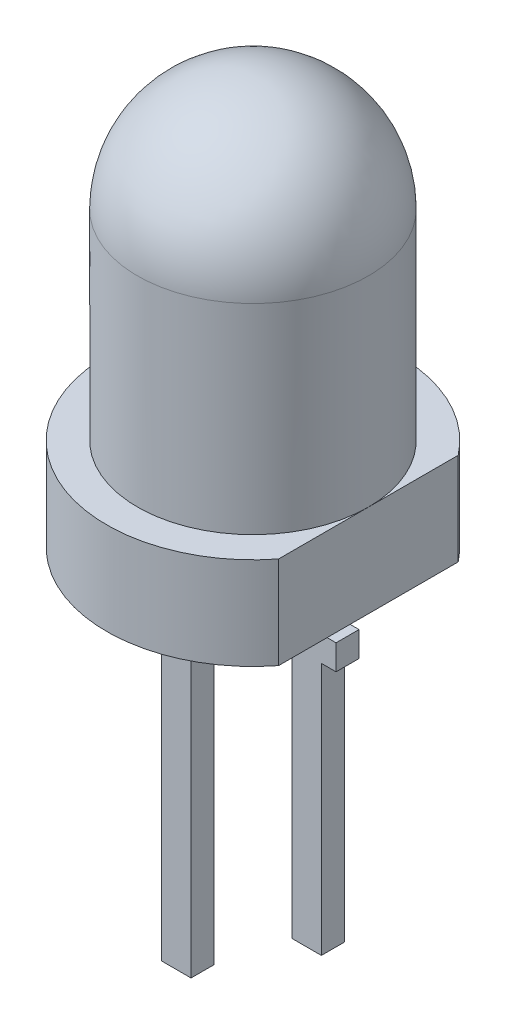
SolidWorks part; units mm, degrees
ref_plane "Front Plane" through (0, 0, 0) normal (0, 0, 1) x (1, 0, 0)
ref_plane "Top Plane" through (0, 0, 0) normal (0, 1, 0) x (1, 0, 0)
ref_plane "Right Plane" through (0, 0, 0) normal (1, 0, 0) x (0, 0, -1)
sketch "Sketch1" plane through (0, 0, 0) normal (0, 0, 1) x (1, 0, 0)
  line L0 (0, 0) -> (0, 27.4114) construction
  line L1 (0, 0) -> (-1.9, 0)
  line L2 (-1.9, 0) -> (-1.9, 1.2)
  line L3 (-1.9, 1.2) -> (-1.5, 1.2)
  line L4 (-1.5, 5.3) -> (-4.9108, 5.3) construction
  line L5 (-1.5, 1.2) -> (-1.5, 3.8)
  line L6 (0, 0) -> (0, 5.3)
  arc A0 (-1.5, 3.8) -> (0, 5.3) centre (0, 3.8) cw
  point P9 (-1.5, 3.8)
  dimension "D6" = 1.5
  dimension "D1" = 1.9
  dimension "D2" = 1.2
  dimension "D3" = 0.4
  dimension "D4" = 5.3
  dimension "D5" = 1.5
  dimension "D7" = 5.3
revolve "Revolve1" add sketch "Sketch1" angle 360 about L6
sketch "Sketch2" plane through (0, 1.2, 0) normal (0, 1, 0) x (1, 0, 0)
  line L0 (1.5, 0) -> (1.5, 1.3049)
  line L1 (1.5, 1.3049) -> (2.0136, 1.3049)
  line L2 (2.0136, 1.3049) -> (2.0136, -1.9254)
  line L3 (2.0136, -1.9254) -> (1.5, -1.9254)
  line L4 (1.5, -1.9254) -> (1.5, 0)
  circle A0 centre (0, 0) radius 1.5 construction
extrude "Cut-Extrude1" cut sketch "Sketch2" against normal blind 10
sketch "Sketch3" plane through (0, 0, 0) normal (0, -1, 0) x (1, 0, 0)
  line L0 (1.5, 0) -> (-1.9, 0) construction
  line L1 (1.5, -1.1662) -> (1.5, 1.1662) construction
  line L2 (0, 0) -> (0, 0.8912) construction
  line L4 (-1.0379, 0.1492) -> (-0.6548, 0.1492)
  line L5 (-1.0379, 0.1492) -> (-1.0379, -0.1492)
  line L6 (-1.0379, -0.1492) -> (-0.6548, -0.1492)
  line L7 (-0.6548, 0.1492) -> (-0.6548, -0.1492)
  line L8 (-1.0379, 0.1492) -> (-0.6548, -0.1492) construction
  line L9 (-1.0379, -0.1492) -> (-0.6548, 0.1492) construction
  line L10 (1.0379, 0.1492) -> (0.6548, 0.1492)
  line L11 (1.0379, 0.1492) -> (1.0379, -0.1492)
  line L12 (1.0379, -0.1492) -> (0.6548, -0.1492)
  line L13 (0.6548, 0.1492) -> (0.6548, -0.1492)
  line L14 (1.0379, 0.1492) -> (0.6548, -0.1492) construction
  line L15 (1.0379, -0.1492) -> (0.6548, 0.1492) construction
  arc A0 (1.5, 1.1662) -> (1.5, -1.1662) centre (0, 0) ccw construction
  dimension "D1" = 0.3831
  dimension "D2" = 0.3831
  dimension "D3" = 0.2985
  dimension "D4" = 0.2985
extrude "Boss-Extrude1" add sketch "Sketch3" along normal blind 4 separate body
sketch "Sketch4" plane through (0, 0, 0) normal (0, 0, 1) x (1, 0, 0)
  line L0 (1.0379, 2.2604) -> (0.2941, 2.7888)
  line L1 (-0.5659, 2.6172) -> (-0.5659, 2.7967)
  line L2 (-1.0379, -0.4146) -> (-1.0379, 2.5705) construction
  line L3 (-1.0379, -4) -> (-1.0379, 0) construction
  line L4 (1.0379, -0.4738) -> (1.0379, 2.2604) construction
  line L5 (1.0379, -4) -> (1.0379, 0) construction
  line L6 (0.4821, 1.5513) -> (-0.6659, 2.3668)
  line L7 (1.1181, 2.2034) -> (-0.1026, 3.0706) construction
  line L8 (1.0379, 2.2604) -> (1.0379, 1.5513)
  line L9 (0.4821, 1.5513) -> (-0.6548, 1.5513)
  line L10 (-1.0379, 2.6172) -> (-1.0379, 1.5513)
  line L12 (-0.3857, 2.7069) -> (0.236, 2.7069)
  line L13 (-0.6659, 2.6172) -> (-0.6659, 2.3668)
  line L14 (-0.5659, 2.6172) -> (-0.5659, 2.4185)
  line L15 (0.6548, 1.5513) -> (-0.5659, 2.4185)
  line L16 (0.5969, 1.4697) -> (-0.6659, 2.3668) construction
  line L17 (0.6548, 0) -> (0.6548, 1.5513) construction
  line L18 (0.6548, 1.5513) -> (0.6548, 0)
  line L19 (1.0379, 1.5513) -> (1.0379, 0)
  line L20 (1.0379, 0) -> (0.6548, 0)
  line L21 (-1.0379, 1.5513) -> (-1.0379, 0)
  line L22 (-0.6548, 0) -> (-0.6548, 1.5513)
  line L23 (-1.0379, 0) -> (-0.6548, 0)
  line L24 (-0.6659, 2.6172) -> (-1.0379, 2.6172)
  line L25 (0.236, 2.7069) -> (0.2941, 2.7888)
  line L26 (-0.5659, 2.7967) -> (-0.5127, 2.7967)
  line L27 (-0.5127, 2.7967) -> (-0.3857, 2.7069)
  point P13 (0, 2.0842)
  dimension "D1" = 0.1
  dimension "D2" = 0.8
extrude "Boss-Extrude2" add sketch "Sketch4" along normal mid plane 0.3
sketch "Sketch5" plane through (0, 2.7069, 0) normal (0, 1, 0) x (1, 0, 0)
  circle A0 centre (-0.0606, 0) radius 0.1894
extrude "Boss-Extrude3" add sketch "Sketch5" along normal blind 0.1 separate body
sketch "Sketch6" plane through (0, 0, 0.1492) normal (0, 0, 1) x (1, 0, 0)
  line L0 (0, 0) -> (0, -1.4446) construction
  line L1 (-0.8463, 0) -> (-0.8463, -1.1017) construction
  line L2 (-0.6548, 0) -> (-1.0379, 0) construction
  line L3 (0.464, -0.7141) -> (1.2287, -0.7141)
  line L4 (-0.464, -0.3876) -> (-1.2287, -0.3876)
  line L5 (-0.464, -0.3876) -> (-0.464, -0.7141)
  line L6 (-0.464, -0.7141) -> (-1.2287, -0.7141)
  line L7 (-1.2287, -0.3876) -> (-1.2287, -0.7141)
  line L8 (-0.464, -0.3876) -> (-1.2287, -0.7141) construction
  line L9 (-0.464, -0.7141) -> (-1.2287, -0.3876) construction
  line L10 (1.2287, -0.3876) -> (1.2287, -0.7141)
  line L11 (0.464, -0.3876) -> (1.2287, -0.3876)
  line L12 (0.464, -0.3876) -> (0.464, -0.7141)
  line L13 (0.464, -0.7141) -> (1.2287, -0.3876) construction
  line L14 (0.464, -0.3876) -> (1.2287, -0.7141) construction
  point P7 (-0.8463, -0.5509)
  point P16 (0.8463, -0.5509)
extrude "Boss-Extrude4" add sketch "Sketch6" against normal up to surface (0.2985 mm away) up to face at (0.7985, -3, -0.1492)
sketch "Sketch7" plane through (0, -4, 0) normal (0, -1, 0) x (1, 0, 0)
  line L4 (-0.6548, -0.1492) -> (-0.6548, 0.1492)
  line L5 (-0.6548, 0.1492) -> (-1.0379, 0.1492)
  line L6 (-1.0379, 0.1492) -> (-1.0379, -0.1492)
  line L7 (-1.0379, -0.1492) -> (-0.6548, -0.1492)
  line L8 (-0.6548, -0.1492) -> (-0.6548, 0.1492)
  line L9 (-0.6548, 0.1492) -> (-1.0379, 0.1492)
  line L10 (-1.0379, 0.1492) -> (-1.0379, -0.1492)
  line L11 (-1.0379, -0.1492) -> (-0.6548, -0.1492)
  dimension "D1" = 0
extrude "Boss-Extrude5" add sketch "Sketch7" along normal blind 1.1
